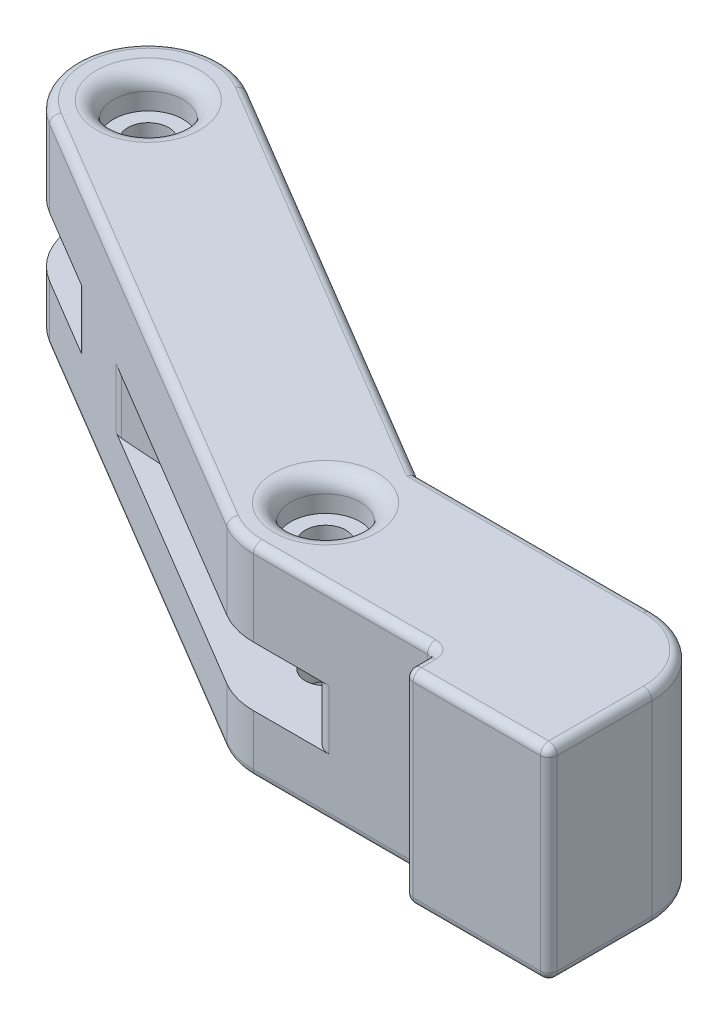
SolidWorks part; units mm, degrees
ref_plane "Front Plane" through (0, 0, 0) normal (0, 0, 1) x (1, 0, 0)
ref_plane "Top Plane" through (0, 0, 0) normal (0, 1, 0) x (1, 0, 0)
ref_plane "Right Plane" through (0, 0, 0) normal (1, 0, 0) x (0, 0, -1)
sketch "Sketch1" plane through (0, 0, 0) normal (0, 1, 0) x (1, 0, 0)
  line L0 (0, 0) -> (0, -15.7) construction
  line L1 (0, 0) -> (-20, -2.5) construction
  line L2 (-20, -2.5) -> (-20, -13.2) construction
  line L5 (-20, -13.2) -> (0, -15.7) construction
  line L6 (-20, -7.85) -> (0, -7.85) construction
  line L7 (-20, -2.5) -> (-0.8489, 13.5697) construction
  line L8 (0, 0) -> (24.9379, -1.7614) construction
  line L9 (-0.8489, 13.5697) -> (24.9379, -1.7614) construction
  line L10 (0, -7.85) -> (48.3923, -7.85) construction
  line L14 (1.323, 17.2228) -> (26.1058, 2.4886)
  line L15 (-3.0208, 9.9166) -> (22.766, -5.4145)
  line L16 (29.1879, -1.7614) -> (39.9379, -1.7614) construction
  line L17 (24.9379, -1.7614) -> (26.1379, -1.7614) construction
  line L18 (26.1058, 2.4886) -> (39.9379, 2.4886)
  line L19 (24.9379, -6.0114) -> (35.6879, -6.0114)
  line L21 (44.1879, -1.7614) -> (44.1879, -7.85)
  line L22 (35.6879, -6.0114) -> (35.6879, -7.85)
  line L23 (35.6879, -7.85) -> (44.1879, -7.85)
  arc A10 (1.323, 17.2228) -> (-3.0208, 9.9166) centre (-0.8489, 13.5697) ccw
  circle A16 centre (-0.8489, 13.5697) radius 1.2
  circle A17 centre (24.9379, -1.7614) radius 1.2
  arc A21 (44.1879, -1.7614) -> (39.9379, 2.4886) centre (39.9379, -1.7614) ccw
  arc A24 (22.766, -5.4145) -> (24.9379, -6.0114) centre (24.9379, -1.7614) ccw
  point P2 (24.9379, -2.6807)
  point P9 (12.0445, 5.9041)
  point P12 (0, 0)
  point P15 (32.4379, -1.7614)
  point P18 (29.1879, -7.85)
  point P21 (0, 0)
  point P23 (0, 0)
  point P26 (44.1669, -7.85)
  point P27 (20.6879, -7.85)
  point P28 (39.9379, -2.6807)
  point P31 (0, 0)
  point P33 (48.3923, -7.85)
  point P35 (36.4259, -7.85)
  point P36 (46.4936, -7.85)
  point P37 (35.6879, -7.85)
  point P38 (0, 0)
  point P39 (24.9379, -7.85)
  point P40 (44.1567, -2.2749)
  point P42 (0, 0)
  point P46 (0, 0)
  point P47 (35.6879, -7.85)
  point P48 (26.1379, 2.4886)
  point P49 (22.766, -5.4145)
  dimension "D4" = 25
  dimension "D5" = 25
  dimension "D16" = 2.4
  dimension "D17" = 1.8386
  dimension "D11" = 4.25
  dimension "D9" = 13.832
  dimension "D10" = 15
  dimension "D15" = 2.4
  dimension "D13" = 4.25
  dimension "D14" = 4.25
  dimension "D1" = 15.7
  dimension "D2" = 10.7
  dimension "D3" = 20
  dimension "D6" = 30
  dimension "D7" = 40
  dimension "D8" = 8.5
  dimension "D12" = 10.75
extrude "Boss-Extrude1" add sketch "Sketch1" along normal blind 12 contours L18 L14 A10 L15 A17 A16 region at (20.0094, 0, -3.1904)
ref_plane "Plane1" through (0, 6, 0) normal (0, 1, 0) x (1, 0, 0)
sketch "Sketch3" plane through (0, 6, 0) normal (0, 1, 0) x (1, 0, 0)
  line L0 (-20, -2.5) -> (-20, -13.2) construction
  line L1 (-20, -13.2) -> (0, -15.7) construction
  line L2 (0, -15.7) -> (0, 0) construction
  line L3 (0, 0) -> (-20, -2.5) construction
  line L4 (-20, -7.85) -> (0, -7.85) construction
  line L5 (-20, -2.5) -> (-0.8489, 13.5697) construction
  line L6 (24.9379, -1.7614) -> (0, 0) construction
  line L7 (-20, -2.5) -> (-0.8489, 13.5697) construction
  line L8 (-22.8925, 0.9472) -> (-3.7414, 17.0169)
  line L10 (0, 0) -> (24.9379, -1.7614) construction
  line L11 (0.3171, 4.4888) -> (25.2549, 2.7274)
  line L12 (-0.3171, -4.4888) -> (17.3396, -5.736)
  line L13 (-0.8489, 13.5697) -> (-13.6248, -7.9193) construction
  line L14 (3.0191, 11.27) -> (-1.0848, 4.3673)
  line L16 (24.9379, -1.7614) -> (12.1619, -23.2504) construction
  line L17 (28.8059, -4.0611) -> (16.03, -25.5501)
  line L19 (1.323, 17.2228) -> (26.1058, 2.4886) construction
  line L20 (17.3396, -5.736) -> (8.2939, -20.9507)
  line L21 (-4.355, -1.1332) -> (-9.7568, -10.2189)
  arc A0 (-22.8925, 0.9472) -> (-17.8859, -6.4725) centre (-20, -2.5) ccw
  arc A2 (0.3171, 4.4888) -> (-1.0848, 4.3673) centre (0, 0) ccw
  arc A4 (3.0191, 11.27) -> (-3.7414, 17.0169) centre (-0.8489, 13.5697) ccw
  arc A5 (-17.8859, -6.4725) -> (-9.7568, -10.2189) centre (-13.6248, -7.9193) ccw
  arc A6 (28.8059, -4.0611) -> (25.2549, 2.7274) centre (24.9379, -1.7614) ccw
  arc A7 (8.2939, -20.9507) -> (16.03, -25.5501) centre (12.1619, -23.2504) ccw
  arc A8 (-4.355, -1.1332) -> (-0.3171, -4.4888) centre (0, 0) ccw
  point P9 (-10.4244, 5.5348)
  point P15 (12.4689, -0.8807)
  point P22 (-7.2369, 2.8252)
  point P27 (18.5499, -12.5059)
  point P34 (14.659, -24.5506)
  dimension "D1" = 20
  dimension "D2" = 10.7
  dimension "D3" = 15.7
  dimension "D4" = 25
  dimension "D5" = 25
  dimension "D6" = 9
  dimension "D10" = 25
  dimension "D11" = 25
extrude "Cut-Extrude1" cut sketch "Sketch3" against normal blind 2.5 and the other way blind 1
sketch "Sketch4" plane through (0, 0, 0) normal (0, -1, 0) x (1, 0, 0)
  line L0 (-0.8489, -13.5697) -> (24.9379, 1.7614) construction
  line L2 (1.1362, -12.3895) -> (-0.8784, -11.2605)
  line L3 (-0.8784, -11.2605) -> (-2.8635, -12.4407)
  line L4 (-2.8635, -12.4407) -> (-2.834, -14.7499)
  line L5 (-2.834, -14.7499) -> (-0.8193, -15.8789)
  line L6 (-0.8193, -15.8789) -> (1.1657, -14.6987)
  line L7 (1.1657, -14.6987) -> (1.1362, -12.3895)
  line L8 (22.9528, 0.5812) -> (24.9674, -0.5478)
  line L9 (24.9674, -0.5478) -> (26.9525, 0.6324)
  line L10 (26.9525, 0.6324) -> (26.9229, 2.9416)
  line L11 (26.9229, 2.9416) -> (24.9083, 4.0706)
  line L12 (24.9083, 4.0706) -> (22.9233, 2.8904)
  line L13 (22.9233, 2.8904) -> (22.9528, 0.5812)
  circle A0 centre (-0.8489, -13.5697) radius 2 construction
  circle A1 centre (24.9379, 1.7614) radius 2 construction
  point P4 (1.1657, -12.3719)
  point P19 (22.9233, 0.5637)
  dimension "D1" = 4
  dimension "D2" = 4
extrude "Cut-Extrude2" cut sketch "Sketch4" against normal blind 2
sketch "Sketch6" plane through (0, 12, 0) normal (0, 1, 0) x (1, 0, 0)
  circle A0 centre (-0.8489, 13.5697) radius 2.05
  circle A1 centre (24.9379, -1.7614) radius 2.05
  dimension "D1" = 4.1
  dimension "D2" = 4.1
extrude "Cut-Extrude3" cut sketch "Sketch6" against normal blind 2
fillet "Fillet1" radius 1 8 edges at (25.8385, 5.25, -2.6475) (27.6463, 5.25, 6.0114) (26.4169, 5.25, -2.4886) (6.8894, 5.25, -4.0246) (2.5943, 5.25, -16.467) (0.8472, 5.25, -7.6169) (24.9379, 12, 3.8114) (-0.8489, 12, -11.5197)
fillet "Fillet2" radius 0.5 23 edges at (35.6879, 12, 6.9307) (35.6879, 0, 6.9307) (44.1879, 0, 4.8057) (33.0219, 0, -2.4886) (30.3129, 12, 6.0114) (23.8117, 12, 5.8595) (9.8726, 12, -2.251) (-4.502, 12, -15.7416) (33.0219, 12, -2.4886) (42.9431, 12, -1.2438) (13.7144, 0, -9.8557) (-4.502, 0, -15.7416) (9.8726, 0, -2.251) (23.8117, 0, 5.8595) (42.9431, 0, -1.2438) (13.7144, 12, -9.8557) (44.1879, 12, 4.8057) (39.9379, 0, 7.85) (44.1879, 6, 7.85) (35.6879, 6, 7.85) (39.9379, 12, 7.85) (35.6879, 6, 6.0114) (30.3129, 0, 6.0114)
